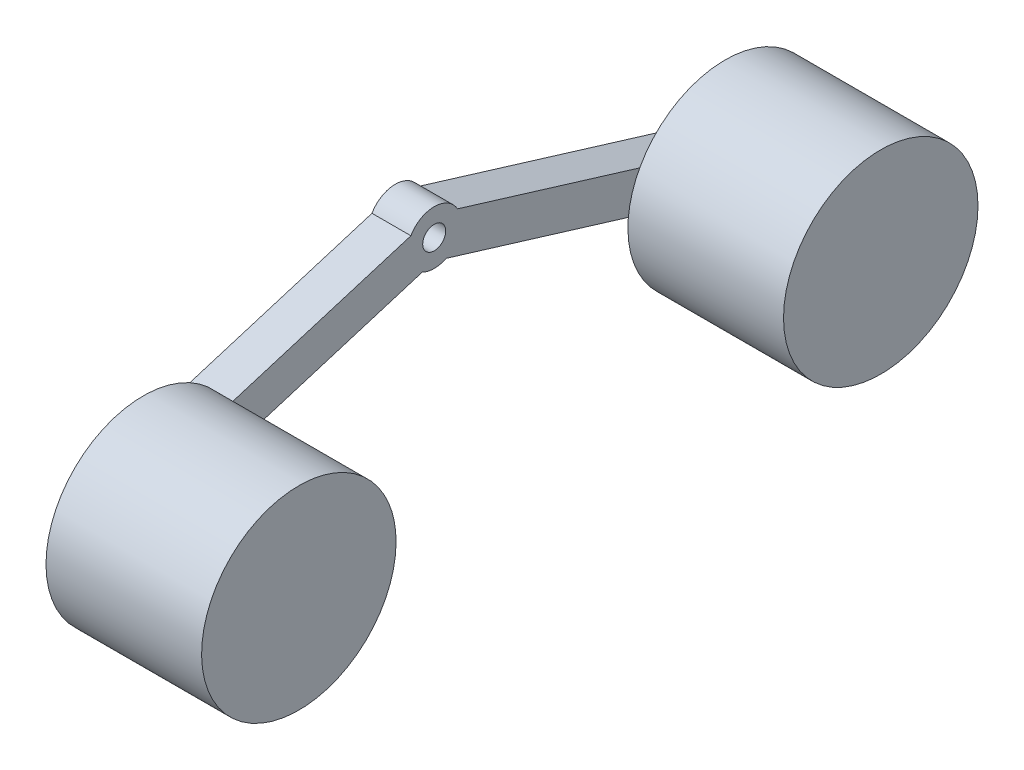
SolidWorks part; units mm, degrees
ref_plane "Front Plane" through (0, 0, 0) normal (0, 0, 1) x (1, 0, 0)
ref_plane "Top Plane" through (0, 0, 0) normal (0, 1, 0) x (1, 0, 0)
ref_plane "Right Plane" through (0, 0, 0) normal (1, 0, 0) x (0, 0, -1)
sketch "Sketch1" plane through (0, 0, 0) normal (1, 0, 0) x (0, 0, -1)
  line L0 (-380, -116) -> (0, 0) construction
  line L1 (0, 0) -> (380, -116) construction
  line L2 (380, -116) -> (-380, -116) construction
  line L3 (-372.5841, -140.2933) -> (0, -26.5571)
  line L4 (0, -26.5571) -> (372.5841, -140.2933)
  line L5 (-387.4159, -91.7067) -> (0, 26.5571)
  line L6 (0, 26.5571) -> (387.4159, -91.7067)
  circle A0 centre (0, 0) radius 35
  circle A1 centre (0, 0) radius 15
  arc A2 (-387.4159, -91.7067) -> (-372.5841, -140.2933) centre (-380, -116) ccw
  arc A3 (387.4159, -91.7067) -> (372.5841, -140.2933) centre (380, -116) cw
  dimension "D5" = 70
  dimension "D6" = 30
  dimension "D3" = 760
  dimension "D4" = 116
  dimension "D2" = 25.4
  dimension "D7" = 25.4
  dimension "D1" = 25.4
extrude "Boss-Extrude1" add sketch "Sketch1" along normal blind 50.8 contours A3 L6 A0 L4 | L5 A2 L3 A0 | A1 L4 A0 L6 | L3 A0 L4 | A1 L5 A0 L3 | A1 L6 A0 L5 region at (0, -65.5369, 214.6897) region at (0, -9.9535, 32.6063) region at (0, -31.2978, 0) region at (0, 26.9822, 0) region at (0, -65.5369, -214.6897)
sketch "Sketch2" plane through (50.8, 0, 0) normal (1, 0, 0) x (0, 0, -1)
  circle A0 centre (-380, -116) radius 127
  dimension "D1" = 254
extrude "Boss-Extrude2" add sketch "Sketch2" along normal blind 203.2
sketch "Sketch3" plane through (0, 0, 0) normal (-1, 0, 0) x (0, 0, 1)
  line L2 (380, -116) -> (380, -83.1696) construction
  line L3 (372.8268, -80.9798) -> (371.075, -86.7184)
  line L4 (387.4159, -91.7067) -> (268.4034, -55.3766) construction
  line L5 (371.075, -86.7184) -> (385.4214, -91.0979)
  line L6 (385.4214, -91.0979) -> (387.1732, -85.3593)
  arc A2 (372.8268, -80.9798) -> (387.1732, -85.3593) centre (380, -83.1696) cw
  circle A3 centre (380, -83.1696) radius 2
  dimension "D3" = 4
  dimension "D1" = 15
  dimension "D2" = 6
extrude "Boss-Extrude3" add sketch "Sketch3" against normal blind 5 from offset 4 offset against normal yes
extrude "Boss-Extrude4" add sketch "Sketch3<2>" against normal blind 5 from offset 15 offset against normal yes
sketch "Sketch3<2>" plane through (0, 0, 0) normal (-1, 0, 0) x (0, 0, 1) same geometry as "Sketch3"
mirror "Mirror1" about plane through (0, 0, 0) normal (0, 0, 1) of "Boss-Extrude4", "Boss-Extrude3", "Boss-Extrude2"
equation "\"D2@Sketch1\"=\"D1@Sketch1\""
equation "\"D7@Sketch1\"=\"D2@Sketch1\""
